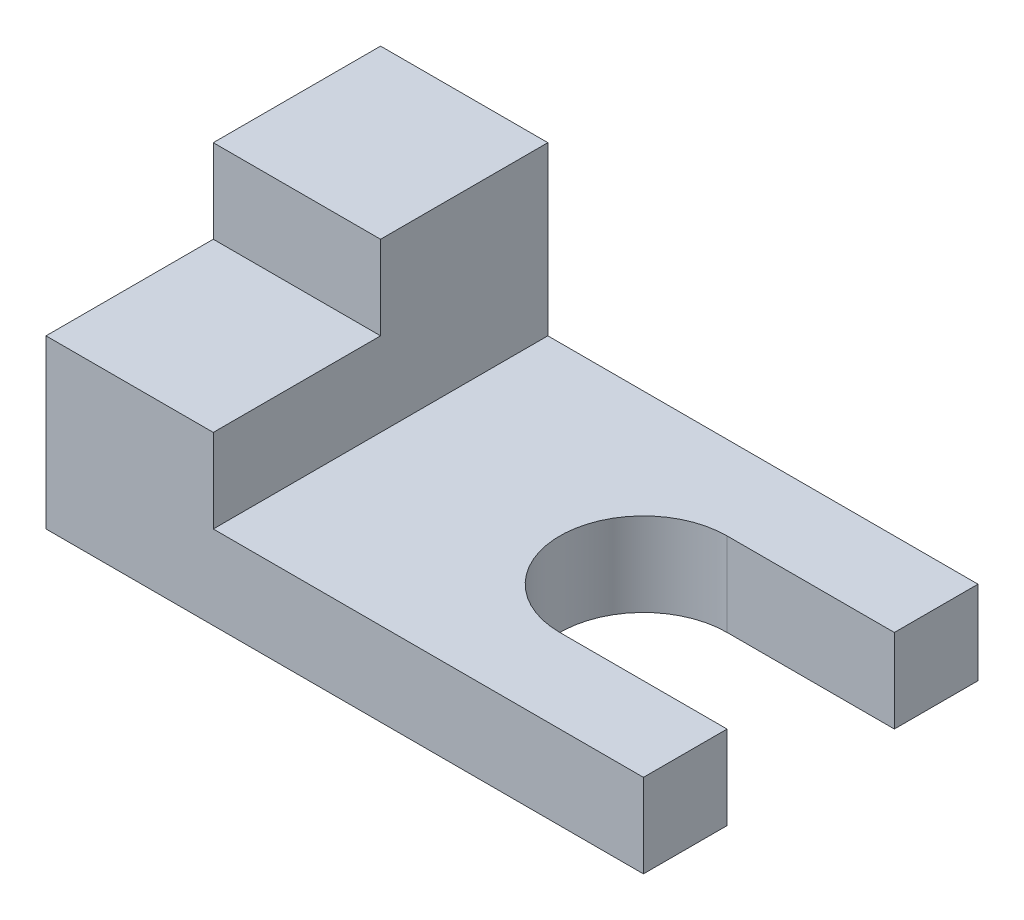
SolidWorks part; units mm, degrees
ref_plane "Front Plane" through (0, 0, 0) normal (0, 0, 1) x (1, 0, 0)
ref_plane "Top Plane" through (0, 0, 0) normal (0, 1, 0) x (1, 0, 0)
ref_plane "Right Plane" through (0, 0, 0) normal (1, 0, 0) x (0, 0, -1)
sketch "Sketch1" plane through (0, 0, 0) normal (0, 1, 0) x (1, 0, 0)
  line L0 (0, 0) -> (-50, 0) construction
  line L1 (0, -7) -> (0, -14)
  line L2 (0, -14) -> (-50, -14)
  line L3 (-50, -14) -> (-50, 0)
  line L4 (-14, -7) -> (0, -7)
  line L5 (-21, 0) -> (-50, 0)
  arc A0 (-21, 0) -> (-14, -7) centre (-14, 0) ccw
  dimension "D3" = 7
  dimension "D1" = 14
  dimension "D2" = 50
  dimension "D4" = 28
extrude "Boss-Extrude1" add sketch "Sketch1" along normal blind 7
mirror "Mirror1" about plane through (-21, 7, 0) normal (0, 0, 1) of bodies 101
sketch "Sketch2" plane through (0, 7, 0) normal (0, 1, 0) x (1, 0, 0)
  line L0 (-36, 14) -> (-36, -14)
  line L1 (-50, 0) -> (-36, 0)
  line L7 (-14, 7) -> (0, 7)
  line L8 (0, 7) -> (0, 14)
  line L9 (0, 14) -> (-50, 14)
  line L10 (-50, 14) -> (-50, -14)
  line L11 (-50, -14) -> (0, -14)
  line L12 (0, -14) -> (0, -7)
  line L13 (0, -7) -> (-14, -7)
  line L14 (-14, 7) -> (0, 7)
  line L15 (0, 7) -> (0, 14)
  line L16 (0, 14) -> (-50, 14)
  line L17 (-50, 14) -> (-50, -14)
  line L18 (-50, -14) -> (0, -14)
  line L19 (0, -14) -> (0, -7)
  line L20 (0, -7) -> (-14, -7)
  arc A1 (-14, 7) -> (-14, -7) centre (-14, 0) ccw
  arc A2 (-14, 7) -> (-14, -7) centre (-14, 0) ccw
  line M12 (0, 14) -> (-50, 14)
  line M13 (-50, 14) -> (-50, -14)
  line M14 (-50, -14) -> (0, -14)
  dimension "D2" = 14
  dimension "D3" = 14
  dimension "D1" = 0
extrude "Boss-Extrude2" add sketch "Sketch2" along normal blind 7 contours L1 L0 M13 M14 region at (-43, 7, 7)
extrude "Boss-Extrude3" add sketch "Sketch2<3>" along normal blind 14 contours L1 L0 M13 M12 region at (-43, 7, -7)
sketch "Sketch2<3>" plane through (0, 7, 0) normal (0, 1, 0) x (1, 0, 0) same geometry as "Sketch2"
